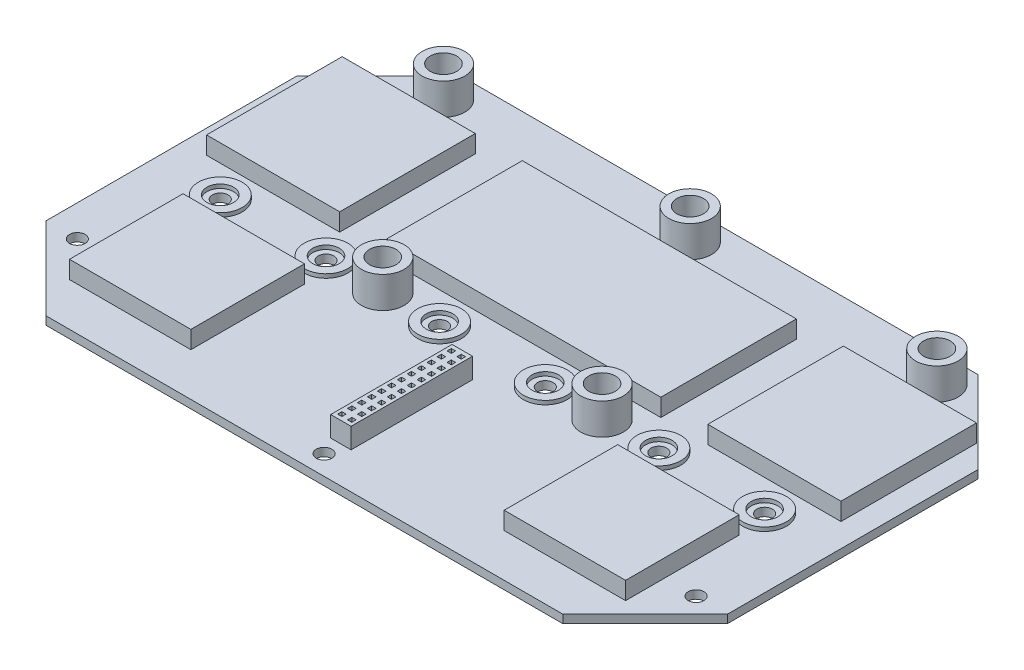
SolidWorks part; units mm, degrees
ref_plane "前视基准面" through (0, 0, 0) normal (0, 0, 1) x (1, 0, 0)
ref_plane "上视基准面" through (0, 0, 0) normal (0, 1, 0) x (1, 0, 0)
ref_plane "右视基准面" through (0, 0, 0) normal (1, 0, 0) x (0, 0, -1)
sketch "草图1" plane through (0, 0, 0) normal (0, 1, 0) x (1, 0, 0)
  line L0 (-87, 32) -> (-66, 53)
  line L1 (-87, -53) -> (87, -53)
  line L2 (-87, -53) -> (-87, 53)
  line L3 (-87, 53) -> (87, 53)
  line L4 (87, -53) -> (87, 53)
  line L5 (-87, -53) -> (87, 53) construction
  line L6 (-87, 53) -> (87, -53) construction
  line L7 (66, 53) -> (87, 32)
  line L8 (-87, -32) -> (-66, -53)
  line L9 (66, -53) -> (87, -32)
  point P0 (0, 0)
  dimension "D1" = 174
  dimension "D2" = 106
  dimension "D3" = 21
  dimension "D4" = 21
  dimension "D5" = 21
  dimension "D6" = 21
extrude "凸台-拉伸1" add sketch "草图1" along normal blind 2.1 contours L1 L9 L4 L7 L3 L0 L2 L8 region at (0, 0, 0)
sketch "草图2" plane through (0, 2.1, 0) normal (0, 1, 0) x (1, 0, 0)
  line L0 (-104.4582, -5) -> (111.7232, -5) construction
  line L1 (0, 63.8138) -> (0, -72.6495) construction
  line L2 (-85.6086, 45.5) -> (100.9239, 45.5) construction
  line L3 (-66, -53) -> (66, -53) construction
  line L4 (-66, 53) -> (66, 53) construction
  circle A0 centre (0, 45.5) radius 2
  circle A1 centre (63, 45.5) radius 2
  circle A2 centre (-63, 45.5) radius 2
  circle A3 centre (-69.5, -5) radius 2
  circle A4 centre (-42.5, -5) radius 2
  circle A5 centre (-28, -5) radius 2
  circle A6 centre (-13.5, -5) radius 2
  circle A7 centre (13.5, -5) radius 2
  circle A8 centre (28, -5) radius 2
  circle A9 centre (42.5, -5) radius 2
  circle A10 centre (69.5, -5) radius 2
  circle A11 centre (79, -32) radius 2
  circle A12 centre (-79, -32) radius 2
  circle A13 centre (0, -48) radius 2
  dimension "D3" = 63
  dimension "D6" = 4
  dimension "D9" = 5
  dimension "D1" = 48
  dimension "D2" = 7.5
  dimension "D4" = 63
  dimension "D5" = 21
  dimension "D7" = 158
  dimension "D8" = 79
  dimension "D10" = 13.5
  dimension "D11" = 13.5
  dimension "D12" = 27
  dimension "D13" = 27
  dimension "D14" = 85
  dimension "D15" = 42.5
  dimension "D16" = 28
  dimension "D17" = 28
extrude "切除-拉伸1" cut sketch "草图2" against normal through all
sketch "草图3" plane through (0, 2.1, 0) normal (0, 1, 0) x (1, 0, 0)
  circle B0 centre (-63, 45.5) radius 3.4
  circle B1 centre (-63, 45.5) radius 5.45
  circle B2 centre (0, 45.5) radius 3.4
  circle B3 centre (0, 45.5) radius 5.45
  circle B4 centre (63, 45.5) radius 3.4
  circle B5 centre (63, 45.5) radius 5.45
  circle B6 centre (-28, -5) radius 3.4
  circle B7 centre (-28, -5) radius 5.45
  circle B8 centre (28, -5) radius 3.4
  circle B9 centre (28, -5) radius 5.45
  circle B10 centre (-42.5, -5) radius 3.4
  circle B11 centre (-42.5, -5) radius 5.6
  circle B12 centre (-69.5, -5) radius 3.4
  circle B13 centre (-69.5, -5) radius 5.6
  circle B14 centre (-13.5, -5) radius 3.4
  circle B15 centre (-13.5, -5) radius 5.6
  circle B16 centre (13.5, -5) radius 3.4
  circle B17 centre (13.5, -5) radius 5.6
  circle B18 centre (42.5, -5) radius 3.4
  circle B19 centre (42.5, -5) radius 5.6
  circle B20 centre (69.5, -5) radius 3.4
  circle B21 centre (69.5, -5) radius 5.6
sketch_block_instance "块1-1"
sketch_block "块1" parameters "D1"=6.8, "D2"=10.9
sketch_block_instance "块1-2"
sketch_block_instance "块1-3"
sketch_block_instance "块1-4"
sketch_block_instance "块1-5"
sketch_block_instance "块2-1"
sketch_block "块2" parameters "D1"=11.2, "D2"=6.8
sketch_block_instance "块2-2"
sketch_block_instance "块2-3"
sketch_block_instance "块2-4"
sketch_block_instance "块2-5"
sketch_block_instance "块2-6"
extrude "凸台-拉伸2" add sketch "草图3" along normal blind 8 separate body contours B1 B0 | B5 B4 | B3 B2 | B7 B6 | B9 B8 region at (-68.2959, 2.1, -45.5) region at (-5.2959, 2.1, -45.5) region at (57.7041, 2.1, -45.5) region at (-33.2959, 2.1, 5) region at (22.7041, 2.1, 5)
extrude "凸台-拉伸3" add sketch "草图3<3>" along normal blind 1 separate body contours B13 B12 | B11 B10 | B15 B14 | B17 B16 | B19 B18 | B21 B20 region at (-47.9416, 2.1, 5) region at (-74.9416, 2.1, 5) region at (-18.9416, 2.1, 5) region at (8.0584, 2.1, 5) region at (37.0584, 2.1, 5) region at (64.0584, 2.1, 5)
sketch "草图3<3>" plane through (0, 2.1, 0) normal (0, 1, 0) x (1, 0, 0) same geometry as "草图3"
sketch "草图4" plane through (0, 2.1, 0) normal (0, 1, 0) x (1, 0, 0)
  line L0 (-66, 53) -> (66, 53) construction
  line L1 (-81, 37.62) -> (81, 37.62)
  line L2 (-81, 37.62) -> (-81, 3)
  line L3 (-81, 3) -> (81, 3)
  line L4 (81, 37.62) -> (81, 3)
  line L5 (10, 50) -> (50, 50)
  line L6 (10, 50) -> (10, 40)
  line L7 (10, 40) -> (50, 40)
  line L8 (50, 50) -> (50, 40)
  line L9 (-50, 50) -> (-10, 50)
  line L10 (-50, 50) -> (-50, 40)
  line L11 (-50, 40) -> (-10, 40)
  line L12 (-10, 50) -> (-10, 40)
  line L13 (-66, -53) -> (66, -53) construction
  line L14 (-71, -13) -> (-40, -13)
  line L15 (-71, -13) -> (-71, -42)
  line L16 (-71, -42) -> (-40, -42)
  line L17 (-40, -13) -> (-40, -42)
  line L18 (40, -13) -> (71, -13)
  line L19 (40, -13) -> (40, -42)
  line L20 (40, -42) -> (71, -42)
  line L21 (71, -13) -> (71, -42)
  line L22 (-47, 37.62) -> (-47, 3)
  line L23 (47, 37.62) -> (47, 3)
  line L24 (-35, 37.62) -> (-35, 3)
  line L25 (35, 37.62) -> (35, 3)
  circle A0 centre (0, 45.5) radius 2 construction
  circle A1 centre (0, -48) radius 2 construction
  circle A3 centre (13.5, -5) radius 2 construction
  circle A4 centre (42.5, -5) radius 2 construction
  dimension "D1" = 10
  dimension "D12" = 8
  dimension "D2" = 10
  dimension "D3" = 40
  dimension "D4" = 40
  dimension "D5" = 10
  dimension "D6" = 3
  dimension "D7" = 81
  dimension "D8" = 81
  dimension "D9" = 40
  dimension "D10" = 40
  dimension "D11" = 11
  dimension "D13" = 142
  dimension "D14" = 8
  dimension "D15" = 34
  dimension "D16" = 34
  dimension "D17" = 34.62
  dimension "D18" = 70
  dimension "D19" = 35
extrude "凸台-拉伸5" add sketch "草图4" along normal blind 4.5 contours L17 L14 L15 L16 | L22 L1 L2 L3 | L25 L1 L24 L3 | L1 L23 L3 L4 | L21 L18 L19 L20 region at (-64, 2.1, -20.31) region at (0, 2.1, -20.31) region at (64, 2.1, -20.31) region at (-55.5, 2.1, 27.5) region at (55.5, 2.1, 27.5)
sketch "草图5" plane through (0, 2.1, 0) normal (0, 1, 0) x (1, 0, 0)
  line L0 (-66, -53) -> (66, -53) construction
  line L1 (-2.605, -12.7) -> (2.605, -12.7)
  line L2 (-2.605, -12.7) -> (-2.605, -43.7)
  line L3 (-2.605, -43.7) -> (2.605, -43.7)
  line L4 (2.605, -12.7) -> (2.605, -43.7)
  point P4 (0, -43.7)
  dimension "D1" = 5.21
  dimension "D2" = 31
  dimension "D3" = 9.3
extrude "凸台-拉伸6" add sketch "草图5" along normal blind 5.21
sketch "草图6" plane through (0, 7.31, 0) normal (0, 1, 0) x (1, 0, 0)
  line L0 (0.72, -42.72) -> (1.82, -42.72)
  line L1 (-1.82, -42.72) -> (-0.72, -42.72)
  line L2 (-1.82, -42.72) -> (-1.82, -41.62)
  line L3 (-1.82, -41.62) -> (-0.72, -41.62)
  line L4 (-0.72, -42.72) -> (-0.72, -41.62)
  line L5 (-1.82, -42.72) -> (-0.72, -41.62) construction
  line L6 (-1.82, -41.62) -> (-0.72, -42.72) construction
  line L7 (0.72, -42.72) -> (0.72, -41.62)
  line L8 (0.72, -41.62) -> (1.82, -41.62)
  line L9 (1.82, -42.72) -> (1.82, -41.62)
  line L10 (0.72, -42.72) -> (1.82, -41.62) construction
  line L11 (0.72, -41.62) -> (1.82, -42.72) construction
  line L12 (0.72, -40.18) -> (1.82, -40.18)
  line L13 (0.72, -40.18) -> (0.72, -39.08)
  line L14 (0.72, -39.08) -> (1.82, -39.08)
  line L15 (1.82, -40.18) -> (1.82, -39.08)
  line L16 (0.72, -40.18) -> (1.82, -39.08) construction
  line L17 (0.72, -39.08) -> (1.82, -40.18) construction
  line L18 (0.72, -37.64) -> (1.82, -37.64)
  line L19 (0.72, -37.64) -> (0.72, -36.54)
  line L20 (0.72, -36.54) -> (1.82, -36.54)
  line L21 (1.82, -37.64) -> (1.82, -36.54)
  line L22 (0.72, -37.64) -> (1.82, -36.54) construction
  line L23 (0.72, -36.54) -> (1.82, -37.64) construction
  line L24 (0.72, -35.1) -> (1.82, -35.1)
  line L25 (0.72, -35.1) -> (0.72, -34)
  line L26 (0.72, -34) -> (1.82, -34)
  line L27 (1.82, -35.1) -> (1.82, -34)
  line L28 (0.72, -35.1) -> (1.82, -34) construction
  line L29 (0.72, -34) -> (1.82, -35.1) construction
  line L30 (0.72, -32.56) -> (1.82, -32.56)
  line L31 (0.72, -32.56) -> (0.72, -31.46)
  line L32 (0.72, -31.46) -> (1.82, -31.46)
  line L33 (1.82, -32.56) -> (1.82, -31.46)
  line L34 (0.72, -32.56) -> (1.82, -31.46) construction
  line L35 (0.72, -31.46) -> (1.82, -32.56) construction
  line L36 (0.72, -30.02) -> (1.82, -30.02)
  line L37 (0.72, -30.02) -> (0.72, -28.92)
  line L38 (0.72, -28.92) -> (1.82, -28.92)
  line L39 (1.82, -30.02) -> (1.82, -28.92)
  line L40 (0.72, -30.02) -> (1.82, -28.92) construction
  line L41 (0.72, -28.92) -> (1.82, -30.02) construction
  line L42 (0.72, -27.48) -> (1.82, -27.48)
  line L43 (0.72, -27.48) -> (0.72, -26.38)
  line L44 (0.72, -26.38) -> (1.82, -26.38)
  line L45 (1.82, -27.48) -> (1.82, -26.38)
  line L46 (0.72, -27.48) -> (1.82, -26.38) construction
  line L47 (0.72, -26.38) -> (1.82, -27.48) construction
  line L48 (0.72, -24.94) -> (1.82, -24.94)
  line L49 (0.72, -24.94) -> (0.72, -23.84)
  line L50 (0.72, -23.84) -> (1.82, -23.84)
  line L51 (1.82, -24.94) -> (1.82, -23.84)
  line L52 (0.72, -24.94) -> (1.82, -23.84) construction
  line L53 (0.72, -23.84) -> (1.82, -24.94) construction
  line L54 (0.72, -22.4) -> (1.82, -22.4)
  line L55 (0.72, -22.4) -> (0.72, -21.3)
  line L56 (0.72, -21.3) -> (1.82, -21.3)
  line L57 (1.82, -22.4) -> (1.82, -21.3)
  line L58 (0.72, -22.4) -> (1.82, -21.3) construction
  line L59 (0.72, -21.3) -> (1.82, -22.4) construction
  line L60 (0.72, -19.86) -> (1.82, -19.86)
  line L61 (0.72, -19.86) -> (0.72, -18.76)
  line L62 (0.72, -18.76) -> (1.82, -18.76)
  line L63 (1.82, -19.86) -> (1.82, -18.76)
  line L64 (0.72, -19.86) -> (1.82, -18.76) construction
  line L65 (0.72, -18.76) -> (1.82, -19.86) construction
  line L66 (0.72, -17.32) -> (1.82, -17.32)
  line L67 (0.72, -17.32) -> (0.72, -16.22)
  line L68 (0.72, -16.22) -> (1.82, -16.22)
  line L69 (1.82, -17.32) -> (1.82, -16.22)
  line L70 (0.72, -17.32) -> (1.82, -16.22) construction
  line L71 (0.72, -16.22) -> (1.82, -17.32) construction
  line L72 (0.72, -14.78) -> (1.82, -14.78)
  line L73 (0.72, -14.78) -> (0.72, -13.68)
  line L74 (0.72, -13.68) -> (1.82, -13.68)
  line L75 (1.82, -14.78) -> (1.82, -13.68)
  line L76 (0.72, -14.78) -> (1.82, -13.68) construction
  line L77 (0.72, -13.68) -> (1.82, -14.78) construction
  line L78 (-1.82, -40.18) -> (-0.72, -40.18)
  line L79 (-1.82, -40.18) -> (-1.82, -39.08)
  line L80 (-1.82, -39.08) -> (-0.72, -39.08)
  line L81 (-0.72, -40.18) -> (-0.72, -39.08)
  line L82 (-1.82, -40.18) -> (-0.72, -39.08) construction
  line L83 (-1.82, -39.08) -> (-0.72, -40.18) construction
  line L84 (-1.82, -37.64) -> (-0.72, -37.64)
  line L85 (-1.82, -37.64) -> (-1.82, -36.54)
  line L86 (-1.82, -36.54) -> (-0.72, -36.54)
  line L87 (-0.72, -37.64) -> (-0.72, -36.54)
  line L88 (-1.82, -37.64) -> (-0.72, -36.54) construction
  line L89 (-1.82, -36.54) -> (-0.72, -37.64) construction
  line L90 (-1.82, -35.1) -> (-0.72, -35.1)
  line L91 (-1.82, -35.1) -> (-1.82, -34)
  line L92 (-1.82, -34) -> (-0.72, -34)
  line L93 (-0.72, -35.1) -> (-0.72, -34)
  line L94 (-1.82, -35.1) -> (-0.72, -34) construction
  line L95 (-1.82, -34) -> (-0.72, -35.1) construction
  line L96 (-1.82, -32.56) -> (-0.72, -32.56)
  line L97 (-1.82, -32.56) -> (-1.82, -31.46)
  line L98 (-1.82, -31.46) -> (-0.72, -31.46)
  line L99 (-0.72, -32.56) -> (-0.72, -31.46)
  line L100 (-1.82, -32.56) -> (-0.72, -31.46) construction
  line L101 (-1.82, -31.46) -> (-0.72, -32.56) construction
  line L102 (-1.82, -30.02) -> (-0.72, -30.02)
  line L103 (-1.82, -30.02) -> (-1.82, -28.92)
  line L104 (-1.82, -28.92) -> (-0.72, -28.92)
  line L105 (-0.72, -30.02) -> (-0.72, -28.92)
  line L106 (-1.82, -30.02) -> (-0.72, -28.92) construction
  line L107 (-1.82, -28.92) -> (-0.72, -30.02) construction
  line L108 (-1.82, -27.48) -> (-0.72, -27.48)
  line L109 (-1.82, -27.48) -> (-1.82, -26.38)
  line L110 (-1.82, -26.38) -> (-0.72, -26.38)
  line L111 (-0.72, -27.48) -> (-0.72, -26.38)
  line L112 (-1.82, -27.48) -> (-0.72, -26.38) construction
  line L113 (-1.82, -26.38) -> (-0.72, -27.48) construction
  line L114 (-1.82, -24.94) -> (-0.72, -24.94)
  line L115 (-1.82, -24.94) -> (-1.82, -23.84)
  line L116 (-1.82, -23.84) -> (-0.72, -23.84)
  line L117 (-0.72, -24.94) -> (-0.72, -23.84)
  line L118 (-1.82, -24.94) -> (-0.72, -23.84) construction
  line L119 (-1.82, -23.84) -> (-0.72, -24.94) construction
  line L120 (-1.82, -22.4) -> (-0.72, -22.4)
  line L121 (-1.82, -22.4) -> (-1.82, -21.3)
  line L122 (-1.82, -21.3) -> (-0.72, -21.3)
  line L123 (-0.72, -22.4) -> (-0.72, -21.3)
  line L124 (-1.82, -22.4) -> (-0.72, -21.3) construction
  line L125 (-1.82, -21.3) -> (-0.72, -22.4) construction
  line L126 (-1.82, -19.86) -> (-0.72, -19.86)
  line L127 (-1.82, -19.86) -> (-1.82, -18.76)
  line L128 (-1.82, -18.76) -> (-0.72, -18.76)
  line L129 (-0.72, -19.86) -> (-0.72, -18.76)
  line L130 (-1.82, -19.86) -> (-0.72, -18.76) construction
  line L131 (-1.82, -18.76) -> (-0.72, -19.86) construction
  line L132 (-1.82, -17.32) -> (-0.72, -17.32)
  line L133 (-1.82, -17.32) -> (-1.82, -16.22)
  line L134 (-1.82, -16.22) -> (-0.72, -16.22)
  line L135 (-0.72, -17.32) -> (-0.72, -16.22)
  line L136 (-1.82, -17.32) -> (-0.72, -16.22) construction
  line L137 (-1.82, -16.22) -> (-0.72, -17.32) construction
  line L138 (-1.82, -14.78) -> (-0.72, -14.78)
  line L139 (-1.82, -14.78) -> (-1.82, -13.68)
  line L140 (-1.82, -13.68) -> (-0.72, -13.68)
  line L141 (-0.72, -14.78) -> (-0.72, -13.68)
  line L142 (-1.82, -14.78) -> (-0.72, -13.68) construction
  line L143 (-1.82, -13.68) -> (-0.72, -14.78) construction
  line L144 (-1.27, -42.17) -> (1.27, -42.17) construction
  line L145 (-2.605, -12.7) -> (-2.605, -43.7) construction
  line L146 (2.605, -43.7) -> (2.605, -12.7) construction
  line L148 (-2.605, -43.7) -> (2.605, -43.7) construction
  line L149 (-1.27, -42.17) -> (-1.27, -39.63) construction
  point P0 (-1.27, -42.17)
  point P8 (1.27, -42.17)
  point P13 (1.27, -39.63)
  point P18 (1.27, -37.09)
  point P23 (1.27, -34.55)
  point P28 (1.27, -32.01)
  point P33 (1.27, -29.47)
  point P38 (1.27, -26.93)
  point P43 (1.27, -24.39)
  point P48 (1.27, -21.85)
  point P53 (1.27, -19.31)
  point P58 (1.27, -16.77)
  point P63 (1.27, -14.23)
  point P68 (-1.27, -39.63)
  point P73 (-1.27, -37.09)
  point P78 (-1.27, -34.55)
  point P83 (-1.27, -32.01)
  point P88 (-1.27, -29.47)
  point P93 (-1.27, -26.93)
  point P98 (-1.27, -24.39)
  point P103 (-1.27, -21.85)
  point P108 (-1.27, -19.31)
  point P113 (-1.27, -16.77)
  point P118 (-1.27, -14.23)
  dimension "D1" = 1.1
  dimension "D2" = 1.1
  dimension "D5" = 2.54
  dimension "D6" = 0.785
  dimension "D7" = 0.785
  dimension "D9" = 0.98
  dimension "D10" = 2.54
  dimension "D3" = 2
  dimension "D4" = 12
extrude "切除-拉伸2" cut sketch "草图6" against normal blind 2
sketch "草图7" plane through (0, 0, 0) normal (0, -1, 0) x (1, 0, 0)
  line L8 (66, 53) -> (-66, 53)
  line L9 (-66, 53) -> (-87, 32)
  line L10 (-87, 32) -> (-87, -32)
  line L11 (-87, -32) -> (-66, -53)
  line L12 (-66, -53) -> (66, -53)
  line L13 (66, -53) -> (87, -32)
  line L14 (87, -32) -> (87, 32)
  line L15 (87, 32) -> (66, 53)
  line L16 (66, 53) -> (-66, 53)
  line L17 (-66, 53) -> (-87, 32)
  line L18 (-87, 32) -> (-87, -32)
  line L19 (-87, -32) -> (-66, -53)
  line L20 (-66, -53) -> (66, -53)
  line L21 (66, -53) -> (87, -32)
  line L22 (87, -32) -> (87, 32)
  line L23 (87, 32) -> (66, 53)
  circle A1 centre (0, -45.5) radius 2
  circle A2 centre (0, -45.5) radius 2
  circle A3 centre (28, 5) radius 2
  circle A4 centre (28, 5) radius 2
  circle A5 centre (13.5, 5) radius 2
  circle A6 centre (13.5, 5) radius 2
  circle A7 centre (-13.5, 5) radius 2
  circle A8 centre (-13.5, 5) radius 2
  circle A9 centre (-28, 5) radius 2
  circle A10 centre (-28, 5) radius 2
  circle A11 centre (-42.5, 5) radius 2
  circle A12 centre (-42.5, 5) radius 2
  circle A13 centre (-69.5, 5) radius 2
  circle A14 centre (-69.5, 5) radius 2
  circle A15 centre (-63, -45.5) radius 2
  circle A16 centre (-63, -45.5) radius 2
  circle A17 centre (63, -45.5) radius 2
  circle A18 centre (63, -45.5) radius 2
  circle A19 centre (42.5, 5) radius 2
  circle A20 centre (42.5, 5) radius 2
  circle A21 centre (69.5, 5) radius 2
  circle A22 centre (69.5, 5) radius 2
  circle A23 centre (79, 32) radius 2
  circle A24 centre (79, 32) radius 2
  circle A25 centre (-79, 32) radius 2
  circle A26 centre (-79, 32) radius 2
  circle A27 centre (0, 48) radius 2
  circle A28 centre (0, 48) radius 2
  dimension "D1" = 0
  dimension "D2" = 0
  dimension "D3" = 0
  dimension "D4" = 0
  dimension "D5" = 0
  dimension "D6" = 0
  dimension "D7" = 0
  dimension "D8" = 0
  dimension "D9" = 0
  dimension "D10" = 0
  dimension "D11" = 0
  dimension "D12" = 0
  dimension "D13" = 0
  dimension "D14" = 0
  dimension "D15" = 0
